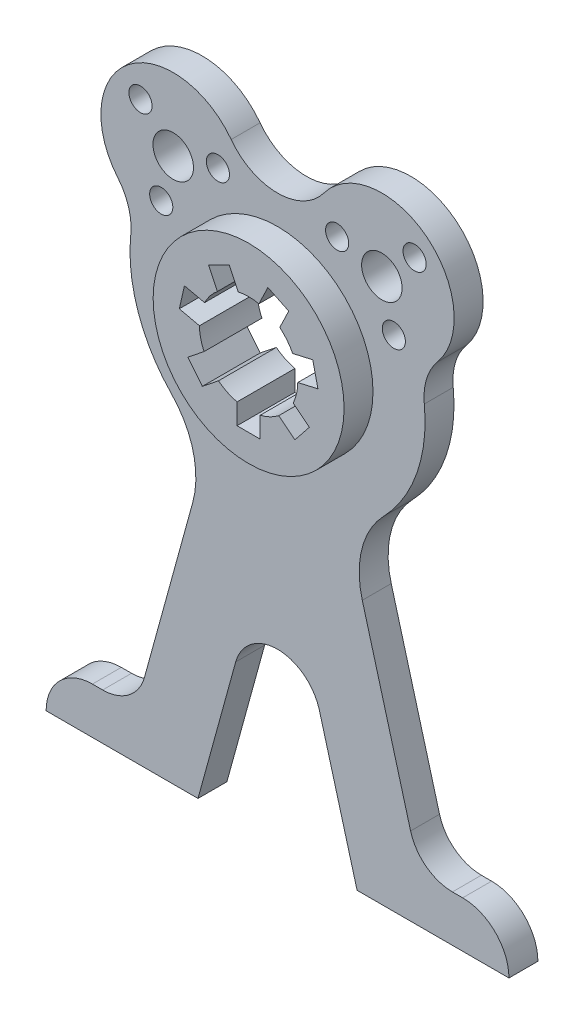
SolidWorks part; units mm, degrees
ref_plane "Спереди" through (0, 0, 0) normal (0, 0, 1) x (1, 0, 0)
ref_plane "Сверху" through (0, 0, 0) normal (0, 1, 0) x (1, 0, 0)
ref_plane "Справа" through (0, 0, 0) normal (1, 0, 0) x (0, 0, -1)
sketch "Эскиз1" plane through (0, 0, 0) normal (0, 0, 1) x (1, 0, 0)
  line L0 (0, 0) -> (0, 62.979) construction
  line L1 (-6.6637, 23.0563) -> (0, 23.0563) construction
  line L2 (0, 23.0563) -> (6.6637, 23.0563) construction
  line L3 (0, 0) -> (-53.7401, 53.7401) construction
  line L4 (-4, -16.5227) -> (-4, -23.6643)
  line L5 (4, -16.5227) -> (4, -23.6643)
  line L6 (4, -23.6643) -> (-4, -23.6643)
  line L7 (-15.4119, -7.1744) -> (-20.9955, -11.6271)
  line L8 (-16.0076, -17.8818) -> (-20.9955, -11.6271)
  line L9 (-10.424, -13.4291) -> (-16.0076, -17.8818)
  line L10 (-15.2184, 7.5764) -> (-22.1809, 9.1655)
  line L11 (-23.9611, 1.3661) -> (-22.1809, 9.1655)
  line L12 (-16.9985, -0.2231) -> (-23.9611, 1.3661)
  line L13 (-3.5651, 16.622) -> (-6.6637, 23.0563)
  line L14 (-13.8714, 19.5853) -> (-6.6637, 23.0563)
  line L15 (-10.7728, 13.1509) -> (-13.8714, 19.5853)
  line L16 (10.7728, 13.1509) -> (13.8714, 19.5853)
  line L17 (6.6637, 23.0563) -> (13.8714, 19.5853)
  line L18 (3.5651, 16.622) -> (6.6637, 23.0563)
  line L19 (16.9985, -0.2231) -> (23.9611, 1.3661)
  line L20 (22.1809, 9.1655) -> (23.9611, 1.3661)
  line L21 (15.2184, 7.5764) -> (22.1809, 9.1655)
  line L22 (10.424, -13.4291) -> (16.0076, -17.8818)
  line L23 (20.9955, -11.6271) -> (16.0076, -17.8818)
  line L24 (15.4119, -7.1744) -> (20.9955, -11.6271)
  line L25 (-80, -152) -> (-27.5, -152)
  line L26 (27.5, -152) -> (80, -152)
  line L27 (0, 0) -> (0, -152) construction
  line L28 (-14.4631, -104.593) -> (-27.5, -152)
  line L29 (45.9969, -124.9773) -> (29.3005, -64.2633)
  line L30 (-27.5, -152) -> (0, -152) construction
  line L31 (-64, -136) -> (-60.4599, -136)
  line L32 (-45.9969, -124.9773) -> (-29.3005, -64.2633)
  line L33 (64, -136) -> (60.4599, -136)
  line L34 (14.4631, -104.593) -> (27.5, -152)
  line L35 (-14.4631, -104.593) -> (0, -52) construction
  line L36 (0, -52) -> (14.4631, -104.593) construction
  line L37 (0, -152) -> (27.5, -152) construction
  circle A0 centre (-36.0624, 36.0624) radius 7
  arc A1 (-10.424, -13.4291) -> (-4, -16.5227) centre (0, 0) ccw
  circle A2 centre (36.0624, 36.0624) radius 7
  arc A3 (-16.0278, 51.0161) -> (16.0278, 51.0161) centre (0, 62.979) ccw
  circle A4 centre (-47.3762, 47.3762) radius 4
  circle A5 centre (-20.6076, 40.2036) radius 4
  circle A6 centre (-40.2036, 20.6076) radius 4
  circle A7 centre (47.3762, 47.3762) radius 4
  circle A8 centre (40.2036, 20.6076) radius 4
  circle A9 centre (20.6076, 40.2036) radius 4
  arc A10 (-16.0278, 51.0161) -> (-55.266, 20.0555) centre (-36.0624, 36.0624) ccw
  arc A11 (16.0278, 51.0161) -> (55.266, 20.0555) centre (36.0624, 36.0624) cw
  arc A12 (-30.7847, 40.6608) -> (-40.6608, 30.7847) centre (0, 0) ccw construction
  arc A13 (-50.7334, 5.2077) -> (-36.6612, -35.4536) centre (0, 0) ccw
  arc A14 (-50.7334, 5.2077) -> (-55.266, 20.0555) centre (-70.6289, 7.2499) ccw
  arc A15 (55.266, 20.0555) -> (50.7334, 5.2077) centre (70.6289, 7.2499) ccw
  arc A16 (-16.9985, -0.2231) -> (-15.4119, -7.1744) centre (0, 0) ccw
  arc A17 (-10.7728, 13.1509) -> (-15.2184, 7.5764) centre (0, 0) ccw
  arc A18 (3.5651, 16.622) -> (-3.5651, 16.622) centre (0, 0) ccw
  arc A19 (15.2184, 7.5764) -> (10.7728, 13.1509) centre (0, 0) ccw
  arc A20 (15.4119, -7.1744) -> (16.9985, -0.2231) centre (0, 0) ccw
  arc A21 (4, -16.5227) -> (10.424, -13.4291) centre (0, 0) ccw
  arc A22 (14.4631, -104.593) -> (-14.4631, -104.593) centre (0, -108.5704) ccw
  arc A23 (-64, -136) -> (-80, -152) centre (-64, -152) ccw
  arc A24 (-45.9969, -124.9773) -> (-60.4599, -136) centre (-60.4599, -121) cw
  arc A25 (29.3005, -64.2633) -> (36.6612, -35.4536) centre (58.2267, -56.3086) cw
  arc A26 (36.6612, -35.4536) -> (50.7334, 5.2077) centre (0, 0) ccw
  arc A27 (45.9969, -124.9773) -> (60.4599, -136) centre (60.4599, -121) ccw
  arc A28 (-29.3005, -64.2633) -> (-36.6612, -35.4536) centre (-58.2267, -56.3086) ccw
  arc A29 (64, -136) -> (80, -152) centre (64, -152) cw
  circle A30 centre (0, 0) radius 24 construction
  circle A31 centre (0, 0) radius 33
  circle A32 centre (-36.0624, 36.0624) radius 16 construction
  arc A33 (0, 51) -> (-36.0624, 36.0624) centre (0, 0) ccw construction
  point P42 (0, 0)
  point P51 (-36.0624, 36.0624)
  point P71 (0, -52)
  dimension "D1" = 45
  dimension "D2" = 34
  dimension "D3" = 8
  dimension "D4" = 48
  dimension "D9" = 102
  dimension "D10" = 14
  dimension "D13" = 8
  dimension "D14" = 51
  dimension "D15" = 25
  dimension "D16" = 20
  dimension "D21" = 25
  dimension "D22" = 55
  dimension "D23" = 160
  dimension "D25" = 15
  dimension "D26" = 16
  dimension "D20" = 15
  dimension "D7" = 20
  dimension "D5" = 66
  dimension "D6" = 32
  dimension "D11" = 20
  dimension "D17" = 30
  dimension "D18" = 100
  dimension "D24" = 16
  dimension "D19" = 152
  dimension "D8" = 7
  dimension "D12" = 3
extrude "Бобышка-Вытянуть1" add sketch "Эскиз1" along normal blind 10 contours A29 L33 A27 L29 A25 A26 A15 A11 A3 A10 A14 A13 A28 L32 A24 L31 A23 L25 L28 A22 L34 L26 A31 A8 A2 A0 A4 A5 A6 A7 A9 region at (0, -49.5016, 0)
extrude "Бобышка-Вытянуть2" add sketch "Эскиз1<3>" along normal blind 20 contours A31 A21 L5 L6 L4 A1 L9 L8 L7 A16 L12 L11 L10 A17 L15 L14 L13 A18 L18 L17 L16 A19 L21 L20 L19 A20 L24 L23 L22 region at (-32.0666, 0, 0)
sketch "Эскиз1<3>" plane through (0, 0, 0) normal (0, 0, 1) x (1, 0, 0) same geometry as "Эскиз1"
